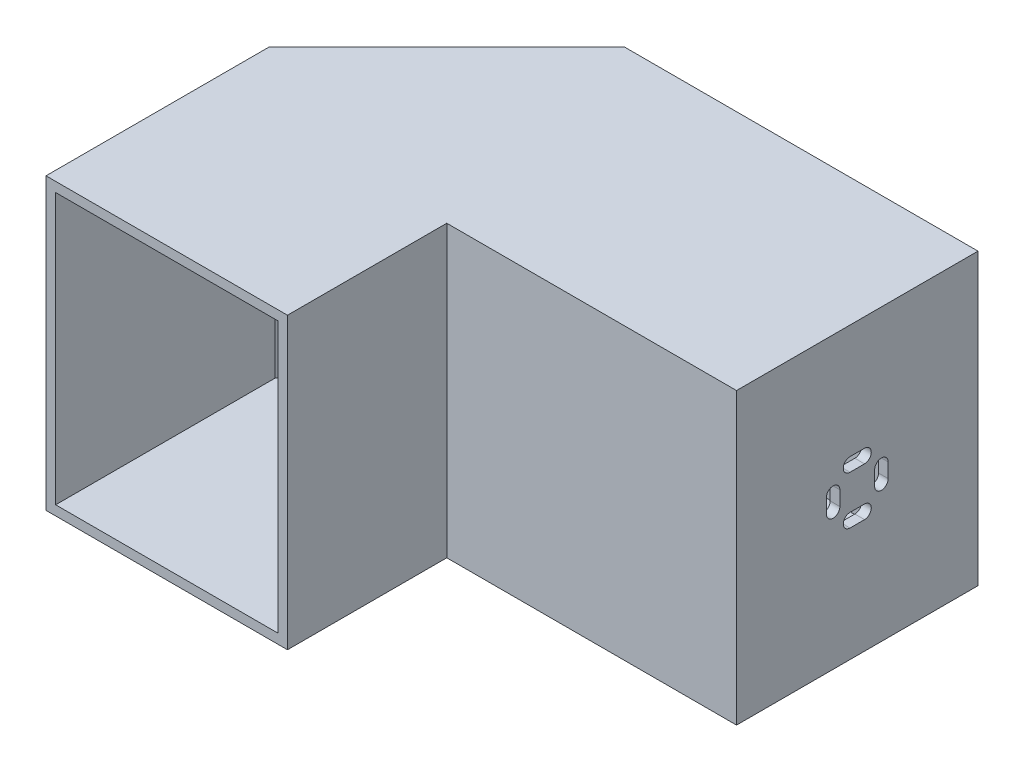
SolidWorks part; units mm, degrees
ref_plane "Front Plane" through (0, 0, 0) normal (0, 0, 1) x (1, 0, 0)
ref_plane "Top Plane" through (0, 0, 0) normal (0, 1, 0) x (1, 0, 0)
ref_plane "Right Plane" through (0, 0, 0) normal (1, 0, 0) x (0, 0, -1)
sketch "Sketch1" plane through (0, 0, 0) normal (0, 1, 0) x (1, 0, 0)
  line L0 (0, 0) -> (0, -41.8923)
  line L1 (0, -41.8923) -> (-63.5, -41.8923)
  line L2 (-63.5, -41.8923) -> (-63.5, 16.8229)
  line L3 (-63.5, 16.8229) -> (-16.8229, 63.5)
  line L4 (76.2, 63.5) -> (76.2, 0)
  line L5 (76.2, 0) -> (0, 0)
  line L6 (-16.8229, 63.5) -> (76.2, 63.5)
  dimension "D1" = 63.5
  dimension "D3" = 63.5
extrude "Boss-Extrude1" add sketch "Sketch1" along normal blind 76.2
shell "Shell1" thickness 2.54 removed face at (-31.75, 38.1, 41.8923)
ref_point "Point1"
sketch "Sketch4" plane through (76.2, 0, 0) normal (1, 0, 0) x (0, 0, -1)
  line L0 (29.845, 44.45) -> (33.655, 44.45) construction
  line L1 (29.845, 46.228) -> (33.655, 46.228)
  line L2 (29.845, 42.672) -> (33.655, 42.672)
  line L3 (0, 76.2) -> (0, 0) construction
  line L4 (0, 76.2) -> (63.5, 76.2) construction
  arc A0 (29.845, 46.228) -> (29.845, 42.672) centre (29.845, 44.45) ccw
  arc A1 (33.655, 42.672) -> (33.655, 46.228) centre (33.655, 44.45) ccw
  point P2 (31.75, 44.45)
  point P9 (0, 38.1)
  point P10 (31.75, 76.2)
  dimension "D2" = 1.778
  dimension "D1" = 3.81
  dimension "D3" = 6.35
  dimension "D4" = 0
ref_axis "Axis1" through (76.2, 38.1, -31.75) along (1, 0, 0)
extrude "Cut-Extrude1" cut sketch "Sketch4" against normal blind 2.54
pattern_circular "CirPattern1" count 4 over 360 about axis through (76.2, 38.1, -31.75) along (1, 0, 0) of "Cut-Extrude1"
